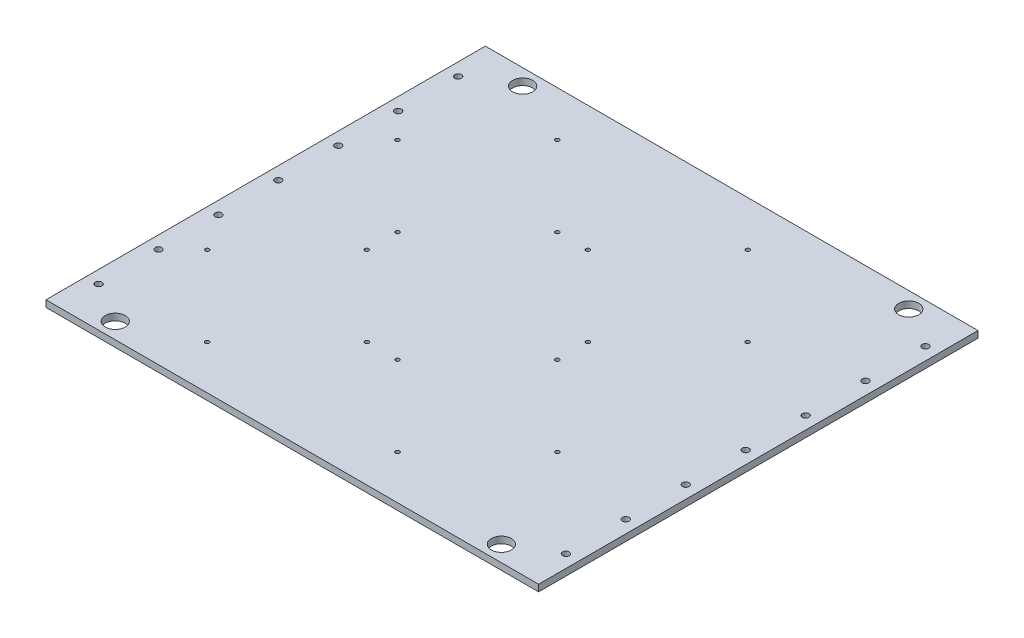
SolidWorks part; units mm, degrees
ref_plane "前视基准面" through (0, 0, 0) normal (0, 0, 1) x (1, 0, 0)
ref_plane "上视基准面" through (0, 0, 0) normal (0, 1, 0) x (1, 0, 0)
ref_plane "右视基准面" through (0, 0, 0) normal (1, 0, 0) x (0, 0, -1)
other "Configuration Table"
sketch "草图1" plane through (0, 0, 0) normal (0, 1, 0) x (1, 0, 0)
  line L1 (185, -165) -> (-185, -165)
  line L2 (185, -165) -> (185, 165)
  line L3 (185, 165) -> (-185, 165)
  line L4 (-185, -165) -> (-185, 165)
  line L5 (185, -165) -> (-185, 165) construction
  line L6 (185, 165) -> (-185, -165) construction
  point P0 (0, 0)
  dimension "D1" = 370
  dimension "D2" = 330
extrude "凸台-拉伸1" add sketch "草图1" along normal blind 5
sketch "草图2" plane through (0, 5, 0) normal (0, 1, 0) x (1, 0, 0)
  circle A0 centre (-159.5, 159) radius 1.6
  circle A1 centre (-128.5, 159) radius 1.6
  circle A2 centre (-159.5, 128) radius 1.6022
  circle A3 centre (-128.5, 128) radius 1.6
  circle A4 centre (128.5, 159) radius 1.6
  circle A5 centre (159.5, 159) radius 1.6
  circle A6 centre (128.5, 128) radius 1.6
  circle A7 centre (159.5, 128) radius 1.6
  circle A8 centre (128.5, -128) radius 1.6
  circle A9 centre (159.5, -128) radius 1.6
  circle A10 centre (159.5, -159) radius 1.6
  circle A11 centre (128.5, -159) radius 1.6
  circle A12 centre (-128.5, -159) radius 1.6
  circle A13 centre (-159.5, -159) radius 1.6
  circle A14 centre (-159.5, -128) radius 1.6
  circle A15 centre (-128.5, -128) radius 1.6
sketch "草图3" plane through (0, 5, 0) normal (0, 1, 0) x (1, 0, 0)
  line L0 (-110, 60) -> (-110, 40)
  line L1 (110, -110) -> (-110, -110) construction
  line L2 (110, -110) -> (110, 110) construction
  line L3 (110, 110) -> (-110, 110) construction
  line L4 (-110, -110) -> (-110, 110) construction
  line L5 (110, -110) -> (-110, 110) construction
  line L6 (110, 110) -> (-110, -110) construction
  line L7 (-110, 110) -> (110, 110)
  line L8 (-110, 110) -> (-110, 90)
  line L9 (-110, 90) -> (110, 90)
  line L10 (110, 110) -> (110, 90)
  line L11 (-110, 60) -> (110, 60)
  line L12 (110, 60) -> (110, 40)
  line L13 (-110, 40) -> (110, 40)
  line L14 (-110, 10) -> (-110, -10)
  line L15 (-110, 10) -> (110, 10)
  line L16 (110, 10) -> (110, -10)
  line L17 (-110, -10) -> (110, -10)
  line L18 (-110, -40) -> (-110, -60)
  line L19 (-110, -40) -> (110, -40)
  line L20 (110, -40) -> (110, -60)
  line L21 (-110, -60) -> (110, -60)
  line L22 (-110, -90) -> (-110, -110)
  line L23 (-110, -90) -> (110, -90)
  line L24 (110, -90) -> (110, -110)
  line L25 (-110, -110) -> (110, -110)
  point P0 (0, 0)
  dimension "D1" = 220
  dimension "D2" = 220
  dimension "D3" = 20
  dimension "D4" = 5
extrude "切除-拉伸2" cut sketch "草图3" against normal through all contours L10 L7 L8 L9 | L0 L13 L12 L11 | L14 L17 L16 L15 | L18 L21 L20 L19 | L22 L25 L24 L23 | L8 L7 L10 L9 | L0 L13 L12 L11 region at (0, 5, -50) region at (0, 5, -100) region at (0, 5, 0) region at (0, 5, 50) region at (0, 5, 100)
sketch "草图8" plane through (0, 5, 0) normal (0, 1, 0) x (1, 0, 0)
  line L0 (120, 0) -> (-120, 0)
  line L1 (0, -120) -> (0, 120)
  point P4 (0, 0)
  point P8 (0, 0)
sketch "草图9" plane through (0, 5, 0) normal (0, 1, 0) x (1, 0, 0)
  line L1 (-117.6798, 117.0824) -> (121.8613, 117.0824)
  line L2 (-117.6798, 117.0824) -> (-117.6798, -116.4851)
  line L3 (-117.6798, -116.4851) -> (121.8613, -116.4851)
  line L4 (121.8613, 117.0824) -> (121.8613, -116.4851)
extrude "凸台-拉伸2" add sketch "草图9" against normal blind 5
sketch "草图12" plane through (0, 5, 0) normal (0, 1, 0) x (1, 0, 0)
  line L0 (185, 0) -> (175.5, 0) construction
  line L1 (185, -165) -> (185, 165) construction
  line L2 (0, -120) -> (0, 120) construction
  line L3 (120, 0) -> (-120, 0) construction
  line L4 (0, -120) -> (0, 120)
  line L5 (120, 0) -> (-120, 0)
  line L6 (-185, 0) -> (-175.5, 0) construction
  circle A0 centre (175.5, 0) radius 2.5
  circle A1 centre (175.5, 45) radius 2.5
  circle A2 centre (175.5, 90) radius 2.5
  circle A3 centre (175.5, 135) radius 2.5
  circle A4 centre (175.5, -135) radius 2.5
  circle A5 centre (175.5, -90) radius 2.5
  circle A6 centre (175.5, -45) radius 2.5
  circle A7 centre (-175.5, -45) radius 2.5
  circle A8 centre (-175.5, -90) radius 2.5
  circle A9 centre (-175.5, -135) radius 2.5
  circle A10 centre (-175.5, 135) radius 2.5
  circle A11 centre (-175.5, 90) radius 2.5
  circle A12 centre (-175.5, 45) radius 2.5
  circle A13 centre (-175.5, 0) radius 2.5
  dimension "D2" = 5
  dimension "D1" = 9.5
  dimension "D3" = 4
extrude "切除-拉伸6" cut sketch "草图12" against normal blind 10 contours A9 | A8 | A7 | A13 | A12 | A11 | A10 | A4 | A5 | A6 | A0 | A1 | A2 | A3 region at (175.5, 5, 0) region at (175.5, 5, -45) region at (175.5, 5, -90) region at (175.5, 5, -135) region at (175.5, 5, 135) region at (175.5, 5, 90) region at (175.5, 5, 45) region at (-175.5, 5, 45) region at (-175.5, 5, 90) region at (-175.5, 5, 135) region at (-175.5, 5, -135) region at (-175.5, 5, -90) region at (-175.5, 5, -45) region at (-175.5, 5, 0)
sketch "草图13" plane through (0, 5, 0) normal (0, 1, 0) x (1, 0, 0)
  line L0 (120, 0) -> (-120, 0) construction
  line L1 (-185, -165) -> (-145, -165)
  line L2 (-185, -165) -> (-185, -153)
  line L3 (-185, -153) -> (-145, -153)
  line L4 (-145, -165) -> (-145, -153)
  line L5 (0, -120) -> (0, 120) construction
  line L6 (120, 0) -> (-120, 0)
  line L7 (0, -120) -> (0, 120)
  circle A1 centre (-145, -153) radius 7.5
  circle A2 centre (145, -153) radius 7.5
  circle A3 centre (145, 153) radius 7.5
  circle A4 centre (-145, 153) radius 7.5
  dimension "D3" = 15
  dimension "D1" = 40
  dimension "D2" = 12
extrude "切除-拉伸7" cut sketch "草图13" against normal blind 10 contours A2 | L4 A1 L3 | L3 A1 L4 | A4 | A3 region at (-148.1831, 5, 156.1831) region at (-143.939, 5, 151.939) region at (145, 5, 153) region at (145, 5, -153) region at (-145, 5, -153)
sketch "草图14" plane through (0, 5, 0) normal (0, 1, 0) x (1, 0, 0)
  circle A0 centre (-97, 131) radius 1.5
  circle A1 centre (-157, 71) radius 1.5
  circle A2 centre (-37, 71) radius 1.5
  circle A3 centre (-97, 11) radius 1.5
  circle A4 centre (-97, -12) radius 1.5
  circle A5 centre (-157, -72) radius 1.5
  circle A6 centre (-97, -132) radius 1.5
  circle A8 centre (-37, -72) radius 1.5
  circle A9 centre (-14, -72) radius 1.5
  circle A10 centre (46, -132) radius 1.5
  circle A11 centre (106, -72) radius 1.5
  circle A12 centre (46, -12) radius 1.5
  circle A13 centre (46, 11) radius 1.5
  circle A14 centre (-14, 71) radius 1.5
  circle A15 centre (106, 71) radius 1.5
  circle A16 centre (46, 131) radius 1.5
extrude "切除-拉伸8" cut sketch "草图14" against normal blind 10
